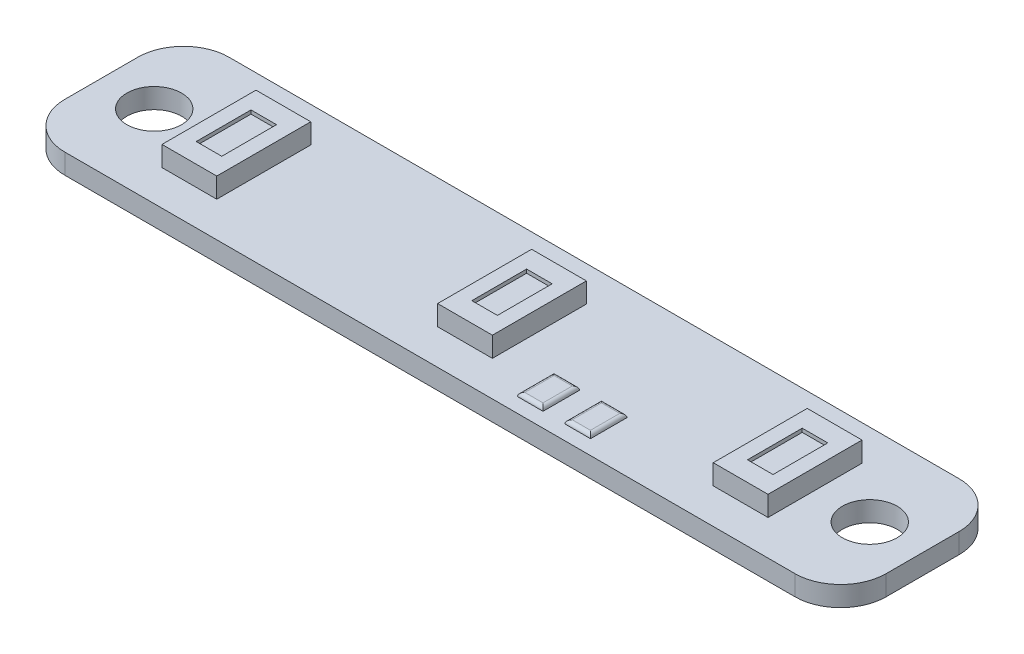
SolidWorks part; units mm, degrees
ref_plane "Front Plane" through (0, 0, 0) normal (0, 0, 1) x (1, 0, 0)
ref_plane "Top Plane" through (0, 0, 0) normal (0, 1, 0) x (1, 0, 0)
ref_plane "Right Plane" through (0, 0, 0) normal (1, 0, 0) x (0, 0, -1)
sketch "Sketch1" plane through (0, 0, 0) normal (0, 1, 0) x (1, 0, 0)
  line L0 (-22.5, 0) -> (22.5, 0) construction
  line L1 (-20, 4.5) -> (20, 4.5)
  line L2 (-22.5, 2) -> (-22.5, -2)
  line L3 (-20, -4.5) -> (20, -4.5)
  line L4 (22.5, 2) -> (22.5, -2)
  line L5 (-22.5, 4.5) -> (22.5, -4.5) construction
  line L6 (-22.5, -4.5) -> (22.5, 4.5) construction
  line L7 (0, -4.5) -> (0, 4.5) construction
  circle A0 centre (-19.6, 0) radius 1.5
  circle A1 centre (19.6, 0) radius 1.5
  arc A2 (20, 4.5) -> (22.5, 2) centre (20, 2) cw
  arc A3 (20, -4.5) -> (22.5, -2) centre (20, -2) ccw
  arc A4 (-22.5, -2) -> (-20, -4.5) centre (-20, -2) ccw
  arc A5 (-20, 4.5) -> (-22.5, 2) centre (-20, 2) ccw
  point P0 (0, 0)
  dimension "D4" = 3
  dimension "D5" = 2.5
  dimension "D1" = 45
  dimension "D2" = 9
  dimension "D3" = 39.2
extrude "Boss-Extrude1" add sketch "Sketch1" along normal blind 1.1
sketch "Sketch2" plane through (0, 1.1, 0) normal (0, 1, 0) x (1, 0, 0)
  line L0 (-22.5, 0) -> (22.5, 0) construction
  line L1 (-22.5, 2) -> (-22.5, -2) construction
  line L2 (22.5, -2) -> (22.5, 2) construction
  line L3 (0, 4.5) -> (0, -4.5) construction
  line L4 (20, 4.5) -> (-20, 4.5) construction
  line L5 (-20, -4.5) -> (20, -4.5) construction
  line L6 (13.6, 2.575) -> (13.6, -2.575)
  line L7 (-16.6, 2.575) -> (-13.6, 2.575)
  line L8 (-16.6, 2.575) -> (-16.6, -2.575)
  line L9 (-16.6, -2.575) -> (-13.6, -2.575)
  line L10 (-13.6, 2.575) -> (-13.6, -2.575)
  line L11 (-16.6, 2.575) -> (-13.6, -2.575) construction
  line L12 (-16.6, -2.575) -> (-13.6, 2.575) construction
  line L13 (-1.5, 2.575) -> (1.5, 2.575)
  line L14 (-1.5, 2.575) -> (-1.5, -2.575)
  line L15 (-1.5, -2.575) -> (1.5, -2.575)
  line L16 (1.5, 2.575) -> (1.5, -2.575)
  line L17 (-1.5, 2.575) -> (1.5, -2.575) construction
  line L18 (-1.5, -2.575) -> (1.5, 2.575) construction
  line L19 (16.6, -2.575) -> (13.6, -2.575)
  line L20 (16.6, 2.575) -> (16.6, -2.575)
  line L21 (16.6, 2.575) -> (13.6, 2.575)
  circle A0 centre (-19.6, 0) radius 1.5 construction
  point P12 (-15.1, 0)
  point P17 (0, 0)
  dimension "D1" = 3
  dimension "D2" = 5.15
  dimension "D3" = 4.5
extrude "Boss-Extrude2" add sketch "Sketch2" along normal blind 1.1
sketch "Sketch3" plane through (0, 2.2, 0) normal (0, 1, 0) x (1, 0, 0)
  line L0 (-16.6, 0) -> (16.6, 0) construction
  line L1 (-16.6, 2.575) -> (-16.6, -2.575) construction
  line L2 (16.6, -2.575) -> (16.6, 2.575) construction
  line L3 (0, 2.575) -> (0, -2.575) construction
  line L4 (1.5, 2.575) -> (-1.5, 2.575) construction
  line L5 (-1.5, -2.575) -> (1.5, -2.575) construction
  line L6 (-15.1, 2.575) -> (-15.1, -2.575) construction
  line L7 (-13.6, 2.575) -> (-16.6, 2.575) construction
  line L8 (-16.6, -2.575) -> (-13.6, -2.575) construction
  line L9 (15.1, 2.575) -> (15.1, -2.575) construction
  line L10 (16.6, 2.575) -> (13.6, 2.575) construction
  line L11 (13.6, -2.575) -> (16.6, -2.575) construction
  line L12 (15.8, -1.5) -> (14.4, -1.5)
  line L13 (-15.8, 1.5) -> (-14.4, 1.5)
  line L14 (-15.8, 1.5) -> (-15.8, -1.5)
  line L15 (-15.8, -1.5) -> (-14.4, -1.5)
  line L16 (-14.4, 1.5) -> (-14.4, -1.5)
  line L17 (-15.8, 1.5) -> (-14.4, -1.5) construction
  line L18 (-15.8, -1.5) -> (-14.4, 1.5) construction
  line L19 (-0.7, 1.5) -> (0.7, 1.5)
  line L20 (-0.7, 1.5) -> (-0.7, -1.5)
  line L21 (-0.7, -1.5) -> (0.7, -1.5)
  line L22 (0.7, 1.5) -> (0.7, -1.5)
  line L23 (-0.7, 1.5) -> (0.7, -1.5) construction
  line L24 (-0.7, -1.5) -> (0.7, 1.5) construction
  line L25 (14.4, 1.5) -> (14.4, -1.5)
  line L26 (15.8, 1.5) -> (14.4, 1.5)
  line L27 (15.8, 1.5) -> (15.8, -1.5)
  point P24 (-15.1, 0)
  point P29 (0, 0)
  dimension "D1" = 1.4
  dimension "D2" = 3
extrude "Cut-Extrude1" cut sketch "Sketch3" against normal blind 0.2
sketch "Sketch4" plane through (0, 1.1, 0) normal (0, 1, 0) x (1, 0, 0)
  line L0 (-20, -4.5) -> (20, -4.5) construction
  line L1 (4, -1.7) -> (8, -1.7)
  line L2 (4, -1.7) -> (4, -3.7)
  line L3 (4, -3.7) -> (8, -3.7)
  line L4 (8, -1.7) -> (8, -3.7)
  line L5 (4, -1.7) -> (8, -3.7) construction
  line L6 (4, -3.7) -> (8, -1.7) construction
  line L7 (22.5, -2) -> (22.5, 2) construction
  line L8 (5.4, -1.7) -> (5.4, -3.7)
  line L9 (6, -1.7) -> (6, -3.7) construction
  line L10 (6.6, -1.7) -> (6.6, -3.7)
  point P0 (6, -2.7)
  dimension "D1" = 4
  dimension "D2" = 2
  dimension "D3" = 0.8
  dimension "D4" = 14.5
  dimension "D5" = 1.4
extrude "Boss-Extrude3" add sketch "Sketch4" along normal blind 0.2 contours L8 L1 L2 L3 | L1 L10 L3 L4 region at (4.7, 1.1, 2.7) region at (7.3, 1.1, 2.7)
fillet "Fillet1" radius 0.2 8 edges at (8, 1.3, 2.7) (7.3, 1.3, 3.7) (6.6, 1.3, 2.7) (7.3, 1.3, 1.7) (4.7, 1.3, 3.7) (4, 1.3, 2.7) (4.7, 1.3, 1.7) (5.4, 1.3, 2.7)
